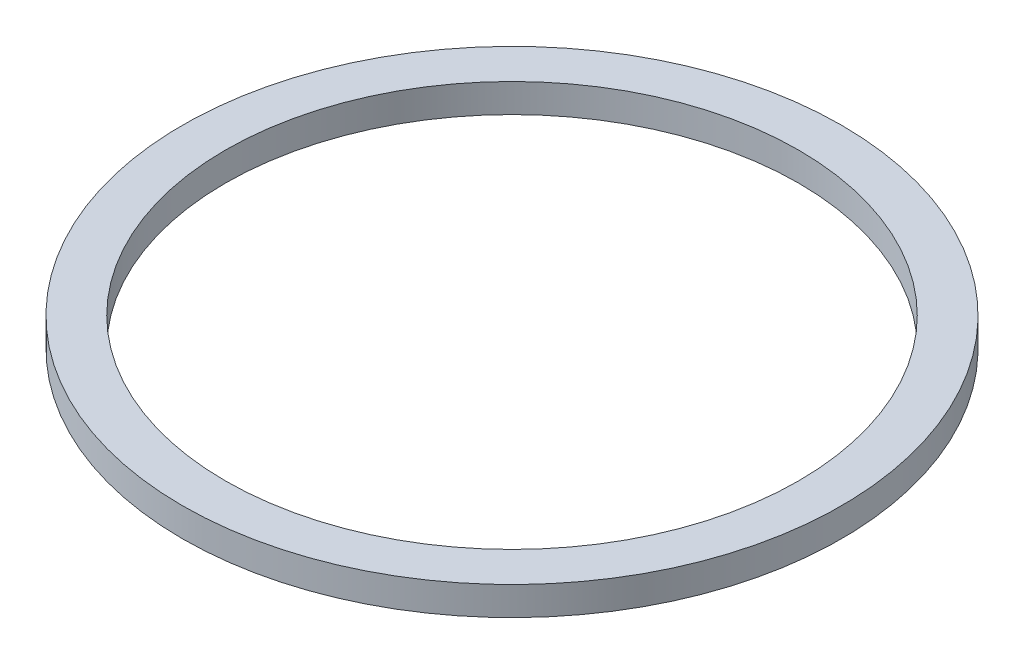
SolidWorks part; units mm, degrees
ref_plane "Front Plane" through (0, 0, 0) normal (0, 0, 1) x (1, 0, 0)
ref_plane "Top Plane" through (0, 0, 0) normal (0, 1, 0) x (1, 0, 0)
ref_plane "Right Plane" through (0, 0, 0) normal (1, 0, 0) x (0, 0, -1)
sketch "Sketch1" plane through (0, 0, 0) normal (0, 1, 0) x (1, 0, 0)
  circle A0 centre (0, 0) radius 57.5
  dimension "FLANGE_OD" = 115
extrude "Boss-Extrude1" add sketch "Sketch1" along normal blind 5
sketch "Sketch2" plane through (0, 0, 0) normal (0, 1, 0) x (1, 0, 0)
  circle A0 centre (0, 0) radius 50
  dimension "BORE_D" = 100
extrude "Cut-Extrude1" cut sketch "Sketch2" along normal through all
sketch "Sketch3" plane through (0, 5, 0) normal (0, 1, 0) x (1, 0, 0)
  circle A0 centre (0, 0) radius 26.3561 construction
  circle A1 centre (-26.3561, 0) radius 1.5
  dimension "BOLT_D" = 3
  dimension "BOLT_PCD" = 52.7123
extrude "Cut-Extrude2" cut sketch "Sketch3" against normal blind 4.1105 rebuild error yes
pattern_circular "CirPattern1" count 6 over 360 rebuild error yes
